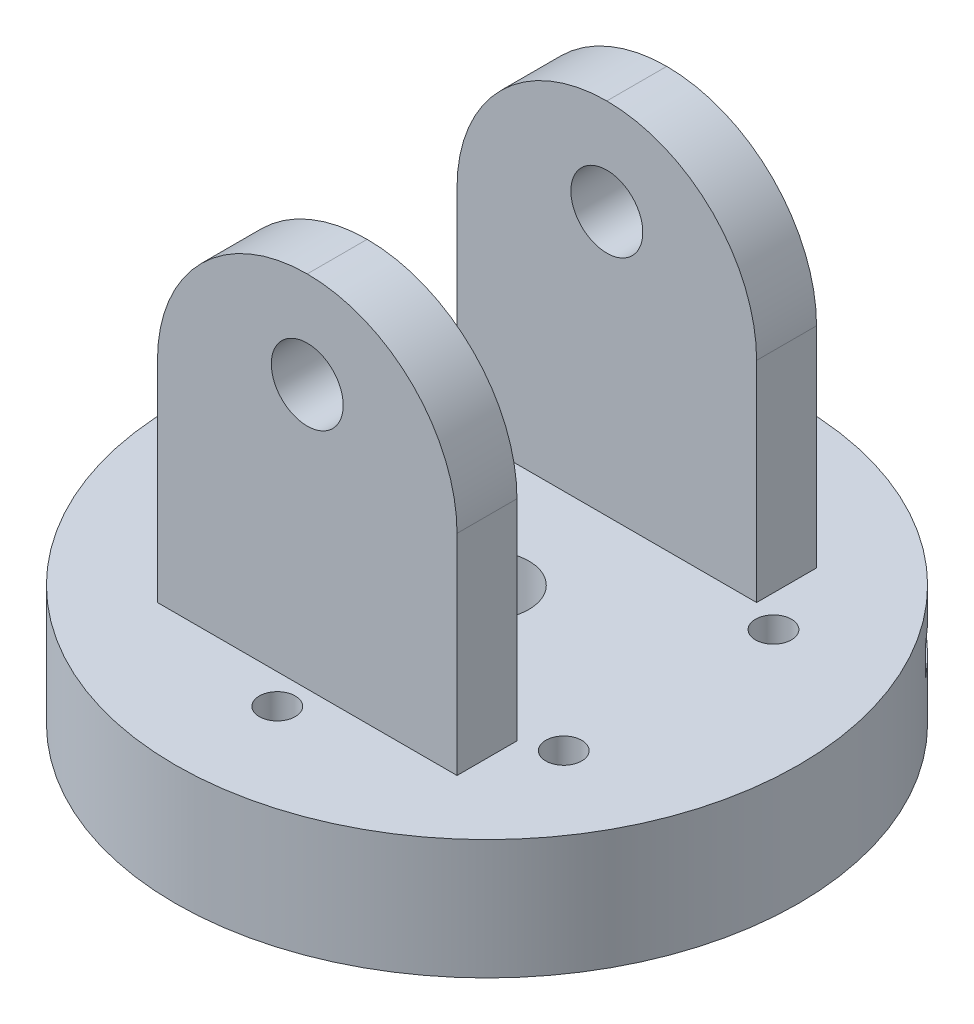
SolidWorks part; units mm, degrees
material "PLA personnalisé"
ref_plane "Plan de face" through (0, 0, 0) normal (0, 0, 1) x (1, 0, 0)
ref_plane "Plan de dessus" through (0, 0, 0) normal (0, 1, 0) x (1, 0, 0)
ref_plane "Plan de droite" through (0, 0, 0) normal (1, 0, 0) x (0, 0, -1)
sketch "Esquisse1" plane through (0, 0, 0) normal (0, 1, 0) x (1, 0, 0)
  circle A0 centre (0, 0) radius 52
  circle A1 centre (0, 0) radius 7
  dimension "D1" = 104
  dimension "D2" = 14
extrude "Boss.-Extru.1" add sketch "Esquisse1" along normal blind 20
sketch "Esquisse2" plane through (0, 20, 0) normal (0, 1, 0) x (1, 0, 0)
  line L0 (0, 0) -> (0, 25) construction
  line L1 (25, 20) -> (-25, 20)
  line L2 (25, 20) -> (25, 30)
  line L3 (-25, 20) -> (-25, 30)
  line L4 (25, 30) -> (-25, 30)
  line L5 (25, 20) -> (-25, 30) construction
  line L6 (-25, 20) -> (25, 30) construction
  line L7 (-34.3845, 0) -> (33.9668, 0) construction
  dimension "D1" = 25
  dimension "D2" = 50
  dimension "D3" = 10
extrude "Boss.-Extru.2" add sketch "Esquisse2" along normal blind 60
fillet "Congé1" radius 25 2 edges at (25, 80, -25) (-25, 80, -25)
sketch "Esquisse3" plane through (0, 0, -30) normal (0, 0, -1) x (-1, 0, 0)
  line L1 (25, 55) -> (25, 20) construction
  line L2 (-25, 20) -> (25, 20) construction
  circle A0 centre (0, 64) radius 6
  dimension "D1" = 44
  dimension "D2" = 12
  dimension "D3" = 25
extrude "Enlèv. mat.-Extru.1" cut sketch "Esquisse3" against normal blind 40
pattern_circular "Répétition circulaire1" count 2 over 360 about axis through (0, 20, 0) along (0, 1, 0) of "Boss.-Extru.2", "Congé1", "Enlèv. mat.-Extru.1"
sketch "Esquisse5" plane through (0, 0, 0) normal (0, -1, 0) x (1, 0, 0)
  circle A0 centre (0, 0) radius 35 construction
  circle A1 centre (0, 35) radius 1.6
  dimension "D1" = 70
  dimension "D2" = 3.2
extrude "Enlèv. mat.-Extru.2" cut sketch "Esquisse5" against normal blind 20
pattern_circular "Répétition circulaire2" count 6 over 360 about axis through (0, 0, 0) along (0, 1, 0) of "Enlèv. mat.-Extru.2"
sketch "Esquisse6" plane through (0, 20, 0) normal (0, 1, 0) x (1, 0, 0)
  circle A0 centre (30.3109, 17.5) radius 3
  circle A1 centre (30.3109, -17.5) radius 3
  circle A2 centre (0, -35) radius 3
  circle A3 centre (-30.3109, -17.5) radius 3
  circle A4 centre (-30.3109, 17.5) radius 3
  circle A5 centre (0, 35) radius 3
  point P16 (0, 0)
  dimension "D1" = 6
  dimension "D2" = 6
extrude "Enlèv. mat.-Extru.3" cut sketch "Esquisse6" against normal blind 9
sketch "Esquisse7" plane through (0, 0, 0) normal (0, 0, 1) x (1, 0, 0)
  line L0 (52, 20) -> (-52, 20) construction
  line L1 (-40.05, 10) -> (40.05, 10)
  line L2 (-40.05, 10) -> (-40.05, 15)
  line L3 (-40.05, 15) -> (40.05, 15)
  line L4 (40.05, 10) -> (40.05, 15)
  line L5 (-40.05, 10) -> (40.05, 15) construction
  line L6 (-40.05, 15) -> (40.05, 10) construction
  line L7 (0, 0) -> (0, 86.6034) construction
  point P4 (0, 12.5)
  dimension "D1" = 5
  dimension "D2" = 5
  dimension "D3" = 80.1
extrude "Enlèv. mat.-Extru.4" cut sketch "Esquisse7" against normal blind 45 from offset 10 offset against normal yes
